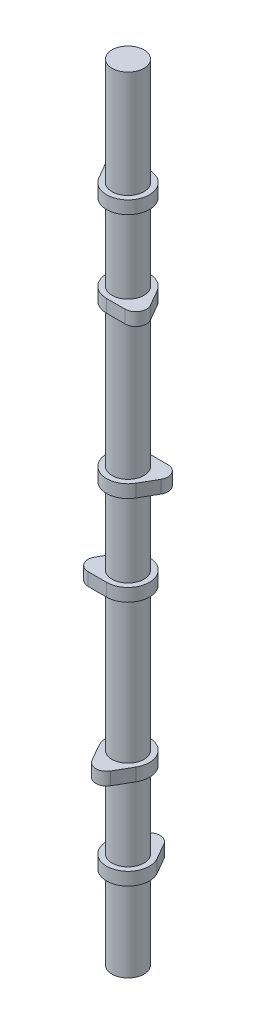
SolidWorks part; units mm, degrees
ref_plane "Front Plane" through (0, 0, 0) normal (0, 0, 1) x (1, 0, 0)
ref_plane "Top Plane" through (0, 0, 0) normal (0, 1, 0) x (1, 0, 0)
ref_plane "Right Plane" through (0, 0, 0) normal (1, 0, 0) x (0, 0, -1)
sketch "Sketch1" plane through (0, 0, 0) normal (0, 1, 0) x (1, 0, 0)
  line L0 (-5.4993, 15.875) -> (-10.9985, 6.35)
  line L1 (5.4993, 15.875) -> (10.9985, 6.35)
  arc A0 (-10.9985, 6.35) -> (10.9985, 6.35) centre (0, 0) ccw
  arc A2 (5.4993, 15.875) -> (-5.4993, 15.875) centre (0, 12.7) ccw
  dimension "D3" = 25.4
  dimension "D1" = 12.7
extrude "Boss-Extrude1" add sketch "Sketch1" along normal blind 7.63
ref_axis "Axis1" through (0, 132.9884, 0) along (0, -1, 0)
pattern_linear "LPattern2" count 2 spacing 53.34 along (0, 1, 0) of bodies 101
move or copy body "Body-Move/Copy1" bodies to move or copy 102 copy no rotation origin (0, 0, 0) rotation axis (0, 1, 0) rotation angle 180
pattern_linear "LPattern3" count 3 spacing 146.05 along (0, 1, 0) of bodies 101 103
move or copy body "Body-Move/Copy2" bodies to move or copy 104 106 copy no rotation origin (0, 0, 0) rotation axis (0, 1, 0) rotation angle 120
move or copy body "Body-Move/Copy3" bodies to move or copy 105 107 copy no rotation origin (0, 0, 0) rotation axis (0, -1, 0) rotation angle 120
sketch "Sketch3" plane through (0, 0, 0) normal (0, 1, 0) x (1, 0, 0)
  circle A0 centre (0, 0) radius 9.5
  dimension "D1" = 19
extrude "Boss-Extrude2" add sketch "Sketch3" along normal blind 466.09 from offset 49.53 offset against normal yes
